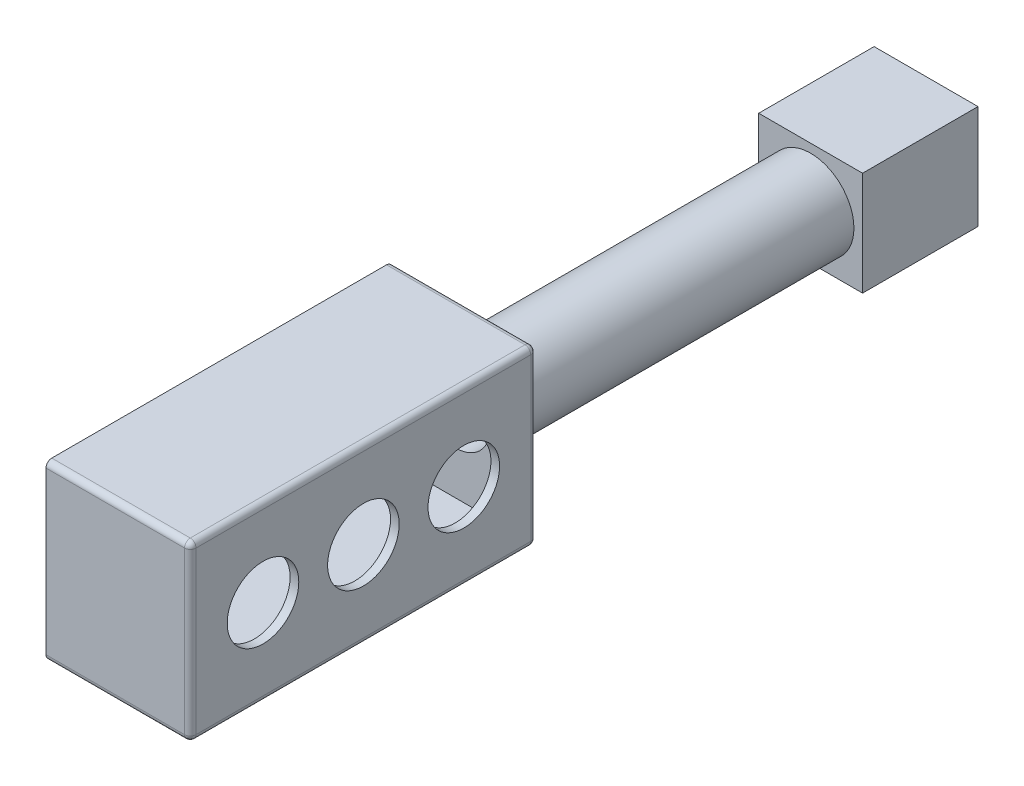
SolidWorks part; units mm, degrees
ref_plane "前视基准面" through (0, 0, 0) normal (0, 0, 1) x (1, 0, 0)
ref_plane "上视基准面" through (0, 0, 0) normal (0, 1, 0) x (1, 0, 0)
ref_plane "右视基准面" through (0, 0, 0) normal (1, 0, 0) x (0, 0, -1)
other "Configuration Table"
sketch "草图1" plane through (0, 0, 0) normal (0, 0, 1) x (1, 0, 0)
  circle A0 centre (0, 0) radius 7.5
  point P4 (0, 0)
extrude "凸台-拉伸1" add sketch "草图1" along normal blind 60
ref_plane "基准面2" through (0, 0, 60) normal (0, 0, 1) x (1, 0, 0)
shell "抽壳3" thickness 1.5 removed face at (7.5, 0, 0) removed face at (7.5, 0, 60)
sketch "草图4" plane through (0, 0, 60) normal (0, 0, 1) x (1, 0, 0)
  line L1 (-12.5, -15) -> (12.5, -15)
  line L2 (-12.5, -15) -> (-12.5, 15)
  line L3 (-12.5, 15) -> (12.5, 15)
  line L4 (12.5, -15) -> (12.5, 15)
  line L5 (-12.5, -15) -> (12.5, 15) construction
  line L6 (-12.5, 15) -> (12.5, -15) construction
  point P0 (0, 0)
  dimension "D1" = 30
  dimension "D2" = 25
extrude "凸台-拉伸4" add sketch "草图4" along normal blind 60
shell "抽壳4" thickness 1.5 removed face at (6, 0, 60) removed face at (-12.5, 0, 90)
ref_plane "基准面3" through (12.5, 0, 0) normal (1, 0, 0) x (0, 0, -1)
sketch "草图5" plane through (12.5, 0, 0) normal (1, 0, 0) x (0, 0, -1)
  line L0 (-120, 0) -> (-60, 0) construction
  line L1 (-120, -15) -> (-120, 15) construction
  line L2 (-60, -7.5) -> (-60, 7.5) construction
  line L3 (-90, 15) -> (-90, -15) construction
  line L4 (-120, 15) -> (-60, 15) construction
  line L5 (-120, -15) -> (-60, -15) construction
  line L6 (-110, 15) -> (-110, -15) construction
  line L7 (-100, 15) -> (-100, -15) construction
  line L8 (-80, 15) -> (-80, -15) construction
  line L9 (-70, 15) -> (-70, -15) construction
  line L10 (-113.6, 2.8731) -> (-113.6, -3.9932) construction
  line L11 (-106.4, 2.8731) -> (-106.4, -3.9932) construction
  line L12 (-86.4, 2.8731) -> (-86.4, -3.9932) construction
  line L13 (-93.6, 2.8731) -> (-93.6, -3.9932) construction
  line L14 (-73.6, 2.8731) -> (-73.6, -3.9932) construction
  line L15 (-66.4, 2.8731) -> (-66.4, -3.9932) construction
  line L16 (-107.4, 2.8731) -> (-107.4, -3.9932) construction
  circle A0 centre (-90, 0) radius 6.2
  circle A5 centre (-107.4, 0) radius 6.2
  circle A6 centre (-72.6, 0) radius 6.2
  dimension "D4" = 6.4
  dimension "D5" = 6.2
  dimension "D1" = 10
  dimension "D2" = 10
  dimension "D3" = 10
extrude "切除-拉伸1" cut sketch "草图5" against normal blind 1.5
sketch "草图18" plane through (0, 0, 0) normal (0, 0, 1) x (1, 0, 0)
  line L1 (-9, -9) -> (9, -9)
  line L2 (-9, -9) -> (-9, 9)
  line L3 (-9, 9) -> (9, 9)
  line L4 (9, -9) -> (9, 9)
  line L5 (-9, -9) -> (9, 9) construction
  line L6 (-9, 9) -> (9, -9) construction
  point P0 (0, 0)
  dimension "D1" = 18
  dimension "D2" = 18
extrude "凸台-拉伸10" add sketch "草图18" against normal blind 20
ref_plane "基准面6" through (0, 0, -1.5) normal (0, 0, 1) x (1, 0, 0)
sketch "草图19" plane through (0, 0, -1.5) normal (0, 0, 1) x (1, 0, 0)
  line L1 (-7.5, 7.5) -> (7.5, 7.5)
  line L2 (-7.5, 7.5) -> (-7.5, -7.5)
  line L3 (-7.5, -7.5) -> (7.5, -7.5)
  line L4 (7.5, 7.5) -> (7.5, -7.5)
  line L5 (-7.5, 7.5) -> (7.5, -7.5) construction
  line L6 (-7.5, -7.5) -> (7.5, 7.5) construction
  point P0 (0, 0)
  dimension "D1" = 15
  dimension "D2" = 15
extrude "切除-拉伸5" cut sketch "草图19" against normal blind 17
sketch "草图20" plane through (0, 0, -1.5) normal (0, 0, 1) x (1, 0, 0)
  circle A0 centre (0, 0) radius 6 construction
  circle A1 centre (0, 0) radius 6
extrude "切除-拉伸6" cut sketch "草图20" along normal blind 1.5
ref_plane "基准面7" through (0, -9, 0) normal (0, -1, 0) x (-1, 0, 0)
sketch "草图22" plane through (0, -9, 0) normal (0, -1, 0) x (-1, 0, 0)
  line L0 (0, 0) -> (0, 20) construction
  line L1 (9, 0) -> (-9, 0) construction
  line L2 (9, 20) -> (-9, 20) construction
  circle A0 centre (0, 10) radius 7.5
  dimension "D2" = 15
  dimension "D1" = 20
extrude "切除-拉伸7" cut sketch "草图22" against normal blind 1.5
fillet "圆角5" radius 1 8 edges at (0, -15, 120) (12.5, -15, 90) (0, -15, 60) (0, 15, 60) (12.5, 0, 60) (12.5, 0, 120) (0, 15, 120) (12.5, 15, 90)
